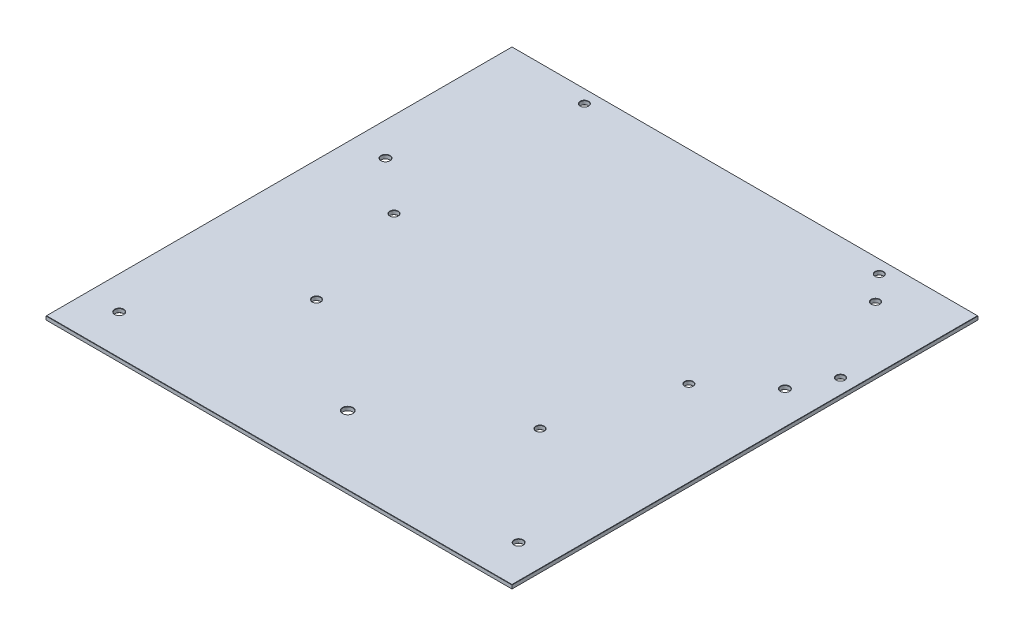
SolidWorks part; units mm, degrees
ref_plane "Front Plane" through (0, 0, 0) normal (0, 0, 1) x (1, 0, 0)
ref_plane "Top Plane" through (0, 0, 0) normal (0, 1, 0) x (1, 0, 0)
ref_plane "Right Plane" through (0, 0, 0) normal (1, 0, 0) x (0, 0, -1)
sketch "Sketch1" plane through (0, 0, 0) normal (0, 1, 0) x (1, 0, 0)
  line L1 (-175, 175) -> (175, 175)
  line L2 (-175, 175) -> (-175, -175)
  line L3 (-175, -175) -> (175, -175)
  line L4 (175, 175) -> (175, -175)
  line L5 (-175, 175) -> (175, -175) construction
  line L6 (-175, -175) -> (175, 175) construction
  point P0 (0, 0)
  dimension "D1" = 350
extrude "Boss-Extrude1" add sketch "Sketch1" along normal blind 3
sketch "Sketch6" plane through (0, 3, 0) normal (0, 1, 0) x (1, 0, 0)
  line L0 (-175, 55) -> (175, 55) construction
  line L1 (-175, 175) -> (-175, -175) construction
  line L2 (175, -175) -> (175, 175) construction
  line L3 (-150, -145) -> (-175, -145) construction
  line L4 (150, -145) -> (175, -145) construction
  line B0 (-150, -145) -> (150, -145) construction
  line B1 (150, -145) -> (150, 55) construction
  line B2 (150, 55) -> (-150, 55) construction
  line B3 (-150, 55) -> (-150, -145) construction
  line B4 (-150, -145) -> (150, 55) construction
  circle B5 centre (-150, -145) radius 3
  circle B6 centre (150, 55) radius 3
  circle B7 centre (150, -145) radius 3
  circle B8 centre (-150, 55) radius 3
sketch_block_instance "Block2-1"
sketch_block "Block2"
sketch "Sketch2" plane through (0, 3, 0) normal (0, 1, 0) x (1, 0, 0)
  line L0 (-175, 175) -> (-175, 55) construction
  line L1 (-175, 175) -> (-175, -175) construction
  line L2 (-175, 55) -> (175, 55) construction
  line L3 (175, -175) -> (175, 175) construction
  line L4 (-155, -175) -> (-155, -155) construction
  line L5 (-175, -175) -> (175, -175) construction
  line L6 (-155, -155) -> (155, -155) construction
  line L7 (155, -155) -> (155, -175) construction
  line L8 (-155, -155) -> (-155, -151.75) construction
  line L9 (155, -155) -> (155, -151.75) construction
  line L10 (155, -151.75) -> (-155, -151.75) construction
  line L11 (-151.75, 55) -> (-151.75, -151.75) construction
  line L12 (-151.75, -151.75) -> (151.75, 55) construction
  line L13 (151.75, 55) -> (151.75, -151.75) construction
  line L14 (151.75, -151.75) -> (-151.75, 55) construction
  line L15 (0, -48.375) -> (0, -123.375) construction
  circle A1 centre (-151.75, -151.75) radius 3.25 construction
  circle A2 centre (151.75, -151.75) radius 3.25 construction
  circle A3 centre (151.75, 55) radius 3.25 construction
  circle A4 centre (-151.75, 55) radius 3.25 construction
  circle A6 centre (0, -123.375) radius 3.75
  circle A7 centre (-150, 55) radius 3 construction
  circle A8 centre (150, 55) radius 3 construction
  circle A9 centre (150, -145) radius 3 construction
  circle A10 centre (-150, -145) radius 3 construction
  circle A11 centre (-150, 55) radius 3 construction
  circle A12 centre (150, 55) radius 3 construction
  circle A13 centre (150, -145) radius 3 construction
  circle A14 centre (-150, -145) radius 3 construction
  circle A15 centre (-150, -145) radius 3.25
  circle A16 centre (-150, 55) radius 3.25
  circle A17 centre (150, 55) radius 3.25
  circle A18 centre (150, -145) radius 3.25
  point P8 (-155, 55)
  point P9 (155, 55)
  dimension "D6" = 6.5
  dimension "D7" = 7.5
  dimension "D8" = 6.5
  dimension "D1" = 120
  dimension "D2" = 20
  dimension "D3" = 20
  dimension "D4" = 20
  dimension "D5" = 75
extrude "Cut-Extrude1" cut sketch "Sketch2" against normal up to surface (3 mm away) up to face at (0, 0, 0)
sketch "Sketch3" plane through (0, 3, 0) normal (0, 1, 0) x (1, 0, 0)
  circle A0 centre (-83.95, -62.9016) radius 3.05 construction
  circle A1 centre (83.95, -62.9016) radius 3.05 construction
  circle A2 centre (-83.95, -62.9016) radius 3.05
  circle A3 centre (83.95, -62.9016) radius 3.05
extrude "Cut-Extrude2" cut sketch "Sketch3" against normal up to surface (3 mm away) up to face at (150, 0, 148.25)
sketch "Sketch4" plane through (0, 3, 0) normal (0, 1, 0) x (1, 0, 0)
  circle A0 centre (-110.733, 165.1108) radius 3 construction
  circle A1 centre (-110.733, 165.1108) radius 3
  circle A2 centre (-110.75, 22.1108) radius 3 construction
  circle A3 centre (110.75, 22.0845) radius 3 construction
  circle A4 centre (110.767, 165.0845) radius 3 construction
  circle A5 centre (-110.75, 22.1108) radius 3
  circle A6 centre (110.75, 22.0845) radius 3
  circle A7 centre (110.767, 165.0845) radius 3
extrude "Cut-Extrude3" cut sketch "Sketch4" against normal up to surface (3 mm away) up to face at (-83.95, 0, 65.9516)
sketch "Sketch5" plane through (0, 3, 0) normal (0, 1, 0) x (1, 0, 0)
  circle A4 centre (163.7076, 83.0307) radius 3.05 construction
  circle A5 centre (127.4584, 145.5807) radius 3.05 construction
  circle A6 centre (163.7076, 83.0307) radius 3.05
  circle A7 centre (127.4584, 145.5807) radius 3.05
extrude "Cut-Extrude4" cut sketch "Sketch5" against normal up to surface (3 mm away) up to face at (110.767, 0, -162.0845)
chamfer "Chamfer1" distance 0.2 angle 45 34 edges at (0, 0, -175) (-175, 0, 0) (0, 0, 175) (175, 0, 0) (0, 0, 127.125) (83.95, 0, 65.9516) (-83.95, 0, 65.9516) (-110.733, 0, -162.1108) (-110.75, 0, -19.1108) (110.75, 0, -19.0845) (110.767, 0, -162.0845) (127.4584, 0, -142.5307) (163.7076, 0, -79.9807) (0, 3, 175) (-175, 3, 0) (0, 3, -175) (175, 3, 0) (0, 3, 127.125) (83.95, 3, 65.9516) (-83.95, 3, 65.9516) (-110.733, 3, -162.1108) (-110.75, 3, -19.1108) (110.75, 3, -19.0845) (110.767, 3, -162.0845) (127.4584, 3, -142.5307) (163.7076, 3, -79.9807) (-150, 0, 148.25) (-150, 0, -51.75) (150, 0, -51.75) (150, 0, 148.25) (-150, 3, 148.25) (-150, 3, -51.75) (150, 3, -51.75) (150, 3, 148.25)
